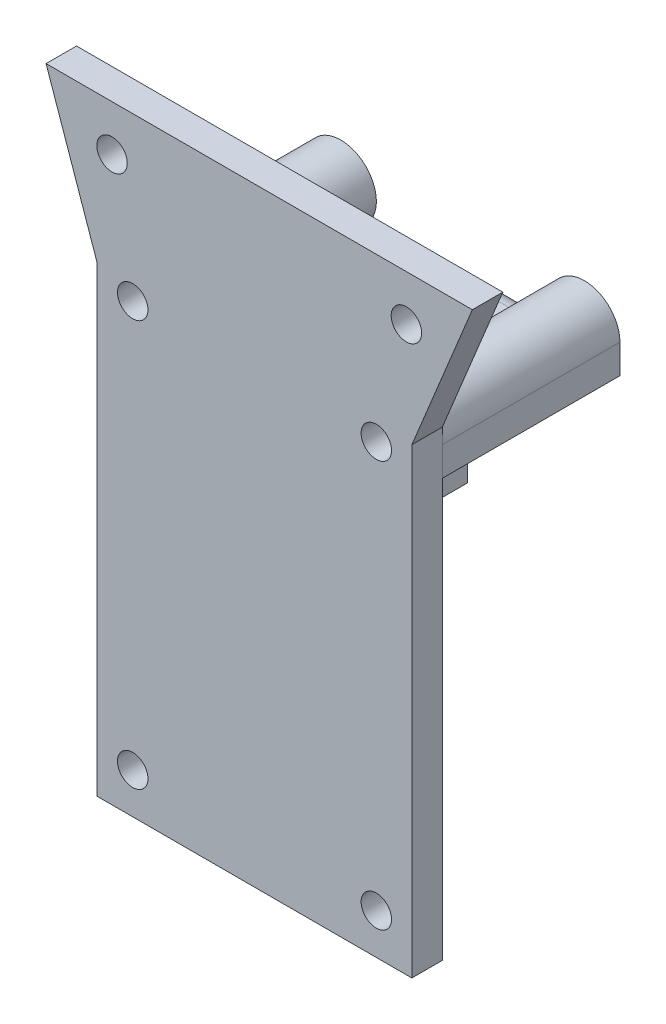
SolidWorks part; units mm, degrees
other "Markup1"
sketch "Sketch10" plane through (36.963, 0, 3) normal (0.1421, -0.5407, 0.8291) x (-0.9838, -0.1695, 0.058)
sketch "Sketch14" plane through (36.963, 0, 3) normal (0.1421, -0.5407, 0.8291) x (-0.9838, -0.1695, 0.058)
sketch "Sketch17" plane through (36.963, 0, 3) normal (0.1421, -0.5407, 0.8291) x (-0.9838, -0.1695, 0.058)
ref_plane "Front Plane" through (0, 0, 0) normal (0, 0, 1) x (1, 0, 0)
ref_plane "Top Plane" through (0, 0, 0) normal (0, 1, 0) x (1, 0, 0)
ref_plane "Right Plane" through (0, 0, 0) normal (1, 0, 0) x (0, 0, -1)
sketch "Sketch1" plane through (0, 0, 0) normal (0, 0, 1) x (1, 0, 0)
  line L1 (0, 0) -> (31, 0)
  line L2 (0, 0) -> (0, 45.5)
  line L3 (-5.037, 60) -> (36.963, 60)
  line L4 (31, 0) -> (31, 45.5)
  line L5 (36.963, 60) -> (31, 45.5)
  line L7 (-5.037, 60) -> (0, 45.5)
  circle A0 centre (30.463, 55.5) radius 1.5
  circle A1 centre (27.5, 44) radius 1.5
  circle A4 centre (27.5, 4) radius 1.5
  circle A5 centre (3.5, 4) radius 1.5
  circle A7 centre (3.5, 44) radius 1.5
  circle A9 centre (1.463, 55.5) radius 1.5
  point P29 (15.963, 60)
  dimension "D4" = 3
  dimension "D5" = 21
  dimension "D6" = 2
  dimension "D7" = 2
  dimension "D8" = 21
  dimension "D9" = 2.5
  dimension "D10" = 37
  dimension "D11" = 2.8
  dimension "D12" = 29
  dimension "D13" = 14.5
  dimension "D14" = 11.5
  dimension "D15" = 3
  dimension "D16" = 5
  dimension "D2" = 0
  dimension "D3" = 31
extrude "Boss-Extrude1" add sketch "Sketch1" along normal blind 3
sketch "Sketch2" plane through (0, 0, 0) normal (0, 0, -1) x (-1, 0, 0)
  line L1 (0, 44) -> (0, 24.5)
  line L3 (0, 45.5) -> (0, 0) construction
  line L4 (0, 24.5) -> (-18, 24.5)
  line L8 (-31, 44) -> (-31, 41.136)
  line L9 (-31, 0) -> (-31, 45.5) construction
  line L11 (-18, 24.5) -> (-18, 28.5)
  line L12 (-18, 28.5) -> (-25, 28.5)
  line L14 (-24.0359, 43.5) -> (-6.9641, 43.5)
  line L16 (-25, 28.5) -> (-25, 35.136)
  line L17 (-25, 35.136) -> (-31, 41.136)
  circle A0 centre (-3.5, 44) radius 1.5 construction
  circle A1 centre (-27.5, 44) radius 1.5 construction
  circle A2 centre (-3.5, 44) radius 1.5 construction
  circle A3 centre (-27.5, 44) radius 1.5 construction
  circle A4 centre (-27.5, 44) radius 2.5
  circle A5 centre (-3.5, 44) radius 2.5
  arc A6 (0, 44) -> (-6.9641, 43.5) centre (-3.5, 44) ccw
  arc A7 (-24.0359, 43.5) -> (-31, 44) centre (-27.5, 44) ccw
  dimension "D1" = 5
  dimension "D2" = 7
  dimension "D3" = 5
  dimension "D4" = 7
  dimension "D6" = 18
  dimension "D9" = 2
  dimension "D10" = 45
  dimension "D11" = 2
  dimension "D8" = 15
  dimension "D5" = 19
  dimension "D7" = 25
extrude "Boss-Extrude2" add sketch "Sketch2" along normal blind 1.5 separate body
sketch "Sketch5" plane through (0, 0, -1.5) normal (0, 0, -1) x (-1, 0, 0)
  line L0 (-23, 41.5) -> (-5.5, 41.5)
  line L1 (-5.5, 42.5) -> (-5.5, 41.5)
  line L2 (-6.9641, 43.5) -> (-24.0359, 43.5) construction
  line L3 (-2, 42) -> (-2, 26.5)
  line L4 (-2, 26.5) -> (-16, 26.5)
  line L5 (-16, 26.5) -> (-16, 30.5)
  line L6 (-16, 30.5) -> (-23, 30.5)
  line L7 (-23, 30.5) -> (-23, 41.5)
  line L11 (-6.9641, 43.5) -> (-24.0359, 43.5)
  line L12 (-31, 44) -> (-31, 41.136)
  line L13 (-31, 41.136) -> (-25, 35.136)
  line L14 (-25, 35.136) -> (-25, 28.5)
  line L15 (-25, 28.5) -> (-18, 28.5)
  line L16 (-18, 28.5) -> (-18, 24.5)
  line L17 (-18, 24.5) -> (0, 24.5)
  line L18 (0, 24.5) -> (0, 44)
  line L19 (-6.9641, 43.5) -> (-24.0359, 43.5)
  line L20 (-31, 44) -> (-31, 41.136)
  line L21 (-31, 41.136) -> (-25, 35.136)
  line L22 (-25, 35.136) -> (-25, 28.5)
  line L23 (-25, 28.5) -> (-18, 28.5)
  line L24 (-18, 28.5) -> (-18, 24.5)
  line L25 (-18, 24.5) -> (0, 24.5)
  line L26 (0, 24.5) -> (0, 44)
  circle A0 centre (-3.5, 44) radius 2.5 construction
  circle A1 centre (-27.5, 44) radius 2.5 construction
  arc A2 (-2, 42) -> (-5.5, 42.5) centre (-3.5, 44) ccw
  arc A3 (0, 44) -> (-6.9641, 43.5) centre (-3.5, 44) ccw
  arc A4 (-24.0359, 43.5) -> (-31, 44) centre (-27.5, 44) ccw
  arc A5 (0, 44) -> (-6.9641, 43.5) centre (-3.5, 44) ccw
  arc A6 (-24.0359, 43.5) -> (-31, 44) centre (-27.5, 44) ccw
  circle A7 centre (-27.5, 44) radius 2.5
  dimension "D1" = 2
  dimension "D3" = 2
  dimension "D4" = 2
  dimension "D5" = 2
  dimension "D6" = 2
  dimension "D7" = 2
  dimension "D8" = 2
  dimension "D2" = 0
extrude "Boss-Extrude5" add sketch "Sketch5" along normal blind 14
sketch "Sketch6" plane through (0, 0, -15.5) normal (0, 0, -1) x (-1, 0, 0)
  line L8 (-6.9641, 43.5) -> (-24.0359, 43.5)
  line L9 (-31, 44) -> (-31, 41.136)
  line L10 (-31, 41.136) -> (-25, 35.136)
  line L11 (-25, 35.136) -> (-25, 28.5)
  line L12 (-25, 28.5) -> (-18, 28.5)
  line L13 (-18, 28.5) -> (-18, 24.5)
  line L14 (-18, 24.5) -> (0, 24.5)
  line L15 (0, 24.5) -> (0, 44)
  line L16 (-6.9641, 43.5) -> (-24.0359, 43.5)
  line L17 (-31, 44) -> (-31, 41.136)
  line L18 (-31, 41.136) -> (-25, 35.136)
  line L19 (-25, 35.136) -> (-25, 28.5)
  line L20 (-25, 28.5) -> (-18, 28.5)
  line L21 (-18, 28.5) -> (-18, 24.5)
  line L22 (-18, 24.5) -> (0, 24.5)
  line L23 (0, 24.5) -> (0, 44)
  arc A1 (-2, 42) -> (-5.5, 42.5) centre (-3.5, 44) ccw construction
  arc A2 (0, 44) -> (-6.9641, 43.5) centre (-3.5, 44) ccw
  arc A3 (-24.0359, 43.5) -> (-31, 44) centre (-27.5, 44) ccw
  arc A4 (0, 44) -> (-6.9641, 43.5) centre (-3.5, 44) ccw
  arc A5 (-24.0359, 43.5) -> (-31, 44) centre (-27.5, 44) ccw
  circle A6 centre (-27.5, 44) radius 2.5 construction
  circle A8 centre (-3.5, 44) radius 2.5
  circle A9 centre (-27.5, 44) radius 2.5
  dimension "D1" = 0
extrude "Boss-Extrude6" add sketch "Sketch6" along normal blind 2
sketch "Sketch8" plane through (0, 0, 0) normal (-1, 0, 0) x (0, 0, 1)
  line L0 (-4, 24.5) -> (-4, 39.5)
  line L1 (-17.5, 24.5) -> (0, 24.5) construction
  line L2 (-4, 39.5) -> (-13.5, 39.5)
  line L3 (-13.5, 39.5) -> (-13.5, 24.5)
  line L4 (-13.5, 24.5) -> (-4, 24.5)
  line L5 (0, 24.5) -> (0, 44) construction
  line L6 (-17.5, 24.5) -> (-17.5, 44) construction
  dimension "D1" = 4
  dimension "D2" = 4
  dimension "D3" = 2
extrude "Cut-Extrude1" cut sketch "Sketch8" against normal blind 3
sketch "Sketch9" plane through (0, 24.5, 0) normal (0, -1, 0) x (1, 0, 0)
  line L0 (10, 0) -> (10, -8)
  line L1 (23.1, 0) -> (-23.1, 0) construction
  line L2 (10, -8) -> (22, -8)
  line L3 (22, -8) -> (22, 0)
  line L4 (22, 0) -> (10, 0)
  line L5 (0, -4) -> (0, 0) construction
  dimension "D1" = 10
  dimension "D2" = 8
  dimension "D3" = 12
extrude "Cut-Extrude2" cut sketch "Sketch9" against normal up to surface (4 mm away) contours L0 L2 L3 L4 up to face at (21.5, 28.5, -8.75)
sketch "Sketch11" plane through (25, 0, 0) normal (1, 0, 0) x (0, 0, -1)
  line L0 (4, 30.5) -> (4, 34.5)
  line L2 (4, 34.5) -> (12, 34.5)
  line L3 (12, 34.5) -> (12, 30.5)
  line L4 (12, 30.5) -> (4, 30.5)
  line L5 (0, 35.136) -> (0, 28.5) construction
  line L6 (17.5, 28.5) -> (0, 28.5) construction
  dimension "D1" = 4
  dimension "D2" = 4
  dimension "D3" = 8
  dimension "D4" = 2
extrude "Cut-Extrude4" cut sketch "Sketch11" against normal blind 2 contours L2 L3 L4 L0
sketch "Sketch12" plane through (0, 0, 0) normal (-1, 0, 0) x (0, 0, 1)
  line L0 (-8.75, 53.5142) -> (-8.75, 17.1339)
  line L1 (-8.75, 17.1339) -> (-21.1273, 17.1339)
  line L2 (-21.1273, 17.1339) -> (-21.1273, 53.5142)
  line L3 (-21.1273, 53.5142) -> (-8.75, 53.5142)
  line L4 (-17.5, 44) -> (0, 44) construction
  point P6 (-8.75, 44)
sketch "Sketch13" plane through (0, 0, 0) normal (0, 0, 1) x (1, 0, 0)
  line L0 (13, 43.5) -> (13, 28.5)
  line L1 (6.9641, 43.5) -> (24.0359, 43.5) construction
  line L2 (25, 28.5) -> (10, 28.5) construction
  line L3 (13, 28.5) -> (18, 28.5)
  line L4 (18, 28.5) -> (18, 43.5)
  line L5 (18, 43.5) -> (13, 43.5)
  line L6 (6.9641, 43.5) -> (24.0359, 43.5) construction
  point P6 (15.5, 43.5)
  point P9 (15.5, 43.5)
  dimension "D1" = 5
extrude "Cut-Extrude7" cut sketch "Sketch13" against normal up to surface (1.5 mm away) up to face at (11.3104, 33.7775, -1.5)
sketch "Sketch15" plane through (0, 43.5, 0) normal (0, 1, 0) x (1, 0, 0)
  line L0 (9.5, 0) -> (9.5, 9.5)
  line L1 (9.5, 9.5) -> (21.5, 9.5)
  line L2 (21.5, 9.5) -> (21.5, 0)
  line L3 (21.5, 0) -> (9.5, 0)
  line L4 (6.9641, 0) -> (13, 0) construction
  line L5 (6.9641, 17.5) -> (24.0359, 17.5) construction
  point P8 (15.5, 17.5)
  point P9 (15.5, 9.5)
  dimension "D1" = 12
  dimension "D2" = 8
extrude "Cut-Extrude8" cut sketch "Sketch15" against normal blind 2
sketch "Sketch16" plane through (-5.068, 5.068, 0) normal (0.7071, -0.7071, 0) x (0, 0, -1)
  line L0 (15.5, 45.6084) -> (1.5, 45.6084) construction
  line L1 (15.5, 45.6084) -> (1.5, 45.6084) construction
  line L2 (0, 53.0581) -> (0, 48.0581) construction
  line L3 (0, 53.0581) -> (0, 48.0581) construction
  line L4 (0, 51.0079) -> (0, 42.5226)
  line L5 (0, 42.5226) -> (17.5, 42.5226)
  line L6 (17.5, 42.5226) -> (17.5, 51.0079)
  line L7 (17.5, 51.0079) -> (0, 51.0079)
  line L8 (0, 51.0079) -> (0, 48.0581) construction
  line L12 (15.5, 45.6084) -> (1.5, 45.6084) construction
  line L13 (0, 48.0581) -> (17.5, 48.0581) construction
  line L14 (4, 49.6084) -> (4, 46.6084)
  line L16 (11, 46.6084) -> (11, 49.6084)
  line L17 (11, 49.6084) -> (4, 49.6084)
  line L20 (4, 40.6586) -> (4, 42.0729) construction
  line L21 (12, 40.6586) -> (12, 42.0729) construction
  line L22 (4, 46.6084) -> (11, 46.6084)
  dimension "D2" = 7
  dimension "D3" = 0
  dimension "D4" = 1
  dimension "D5" = 3
  dimension "D6" = 1
  dimension "D1" = 0
extrude "Cut-Extrude9" cut sketch "Sketch16" against normal through all contours L14 L22 L16 L17
fillet "Fillet1" radius 2 13 edges at (18, 41.5, -0.75) (13, 41.5, -0.75) (13, 28.5, -0.75) (18, 28.5, -0.75) (14.25, 41.5, -15.5) (15.5, 43.5, -17.5) (25, 28.5, -8.75) (18, 24.5, -12.75) (16, 30.5, -8.5) (18, 28.5, -12.75) (0, 24.5, -15.5) (0, 24.5, -2) (2, 26.5, -2.75)
sketch "Sketch21" plane through (0, 0, -17.5) normal (0, 0, -1) x (-1, 0, 0)
  line L1 (-25, 35.136) -> (-16, 35.136)
  line L2 (-25, 35.136) -> (-25, 24.5)
  line L3 (-25, 24.5) -> (-16, 24.5)
  line L4 (-16, 35.136) -> (-16, 24.5)
  point P4 (0, 0)
extrude "Cut-Extrude11" cut sketch "Sketch21" against normal up to surface (16 mm away) up to face at (8.0848, 34.6967, -1.5)
sketch "Sketch19" plane through (0, 24.5, 0) normal (0, -1, 0) x (1, 0, 0)
  line L4 (16, -17.5) -> (2, -17.5) construction
  line L6 (0, -17.5) -> (0, 0) construction
  line L7 (10, 0) -> (2, 0) construction
  circle A0 centre (9, -8.5) radius 7
  dimension "D1" = 1.5
  dimension "D2" = 2
  dimension "D3" = 2
sketch "Sketch23" plane through (0, 24.5, 0) normal (0, -1, 0) x (1, 0, 0)
  circle A0 centre (9, -8.5) radius 6
  circle A1 centre (9, -8.5) radius 7 construction
  dimension "D1" = 1
extrude "Boss-Extrude7" add sketch "Sketch23" against normal blind 2
fillet "Fillet2" radius 2 4 edges at (16, 35.136, -16.5) (1, 39.5, -13.5) (1, 39.5, -4) (24, 35.136, -1.5)
